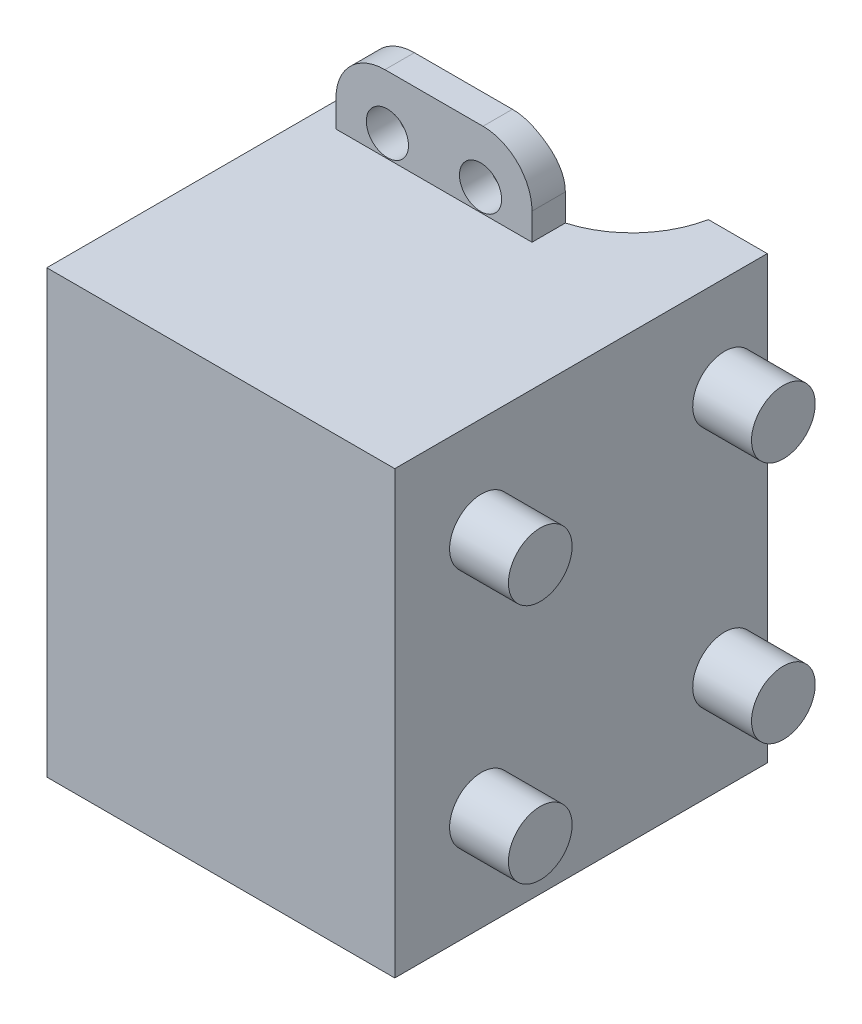
SolidWorks part; units mm, degrees
ref_plane "Front Plane" through (0, 0, 0) normal (0, 0, 1) x (1, 0, 0)
ref_plane "Top Plane" through (0, 0, 0) normal (0, 1, 0) x (1, 0, 0)
ref_plane "Right Plane" through (0, 0, 0) normal (1, 0, 0) x (0, 0, -1)
sketch "Sketch1" plane through (0, 0, 0) normal (0, 0, 1) x (1, 0, 0)
  line L1 (-13.1579, 24.7807) -> (11.8421, 24.7807)
  line L2 (-13.1579, 24.7807) -> (-13.1579, -20.2193)
  line L3 (-13.1579, -20.2193) -> (11.8421, -20.2193)
  line L4 (11.8421, 24.7807) -> (11.8421, -20.2193)
  dimension "D1" = 25
  dimension "D2" = 45
extrude "Boss-Extrude1" add sketch "Sketch1" along normal blind 30
sketch "Sketch2" plane through (0, 0, 0) normal (0, 0, -1) x (-1, 0, 0)
  line L0 (-11.8421, -20.2193) -> (-11.8421, 24.7807) construction
  line L1 (-9.5921, 22.5307) -> (10.9079, 22.5307)
  line L2 (-9.5921, 22.5307) -> (-9.5921, -17.9693)
  line L3 (-9.5921, -17.9693) -> (10.9079, -17.9693)
  line L4 (10.9079, 22.5307) -> (10.9079, -17.9693)
  line L6 (-11.8421, 24.7807) -> (13.1579, 24.7807) construction
  dimension "D1" = 20.5
  dimension "D2" = 40.5
  dimension "D3" = 2.25
  dimension "D4" = 2.25
extrude "Cut-Extrude1" cut sketch "Sketch2" against normal blind 28
sketch "Sketch3" plane through (0, 0, 0) normal (0, 0, -1) x (-1, 0, 0)
  line L0 (-11.8421, 24.7807) -> (13.1579, 24.7807) construction
  line L1 (-9.3421, 24.7807) -> (10.6579, 24.7807)
  line L2 (-9.3421, 24.7807) -> (-9.3421, 32.5307)
  line L3 (-9.3421, 32.5307) -> (10.6579, 32.5307)
  line L4 (10.6579, 24.7807) -> (10.6579, 32.5307)
  line L5 (13.1579, 24.7807) -> (13.1579, -20.2193) construction
  line L7 (-11.8421, 2.2807) -> (13.1579, 2.2807) construction
  line L8 (-11.8421, -20.2193) -> (-11.8421, 24.7807) construction
  line L9 (-9.3421, -27.9693) -> (10.6579, -27.9693)
  line L10 (10.6579, -20.2193) -> (10.6579, -27.9693)
  line L11 (-9.3421, -20.2193) -> (10.6579, -20.2193)
  line L12 (-9.3421, -20.2193) -> (-9.3421, -27.9693)
  dimension "D1" = 7.75
  dimension "D2" = 20
  dimension "D3" = 2.5
extrude "Boss-Extrude2" add sketch "Sketch3" against normal blind 3
sketch "Sketch5" plane through (0, -17.9693, 0) normal (0, 1, 0) x (1, 0, 0)
  line L0 (9.5921, 0) -> (-10.9079, 0) construction
  line L1 (-4.6579, 0) -> (3.3421, 0)
  line L2 (-4.6579, 0) -> (-4.6579, -28)
  line L3 (-4.6579, -28) -> (3.3421, -28)
  line L4 (3.3421, 0) -> (3.3421, -28)
  line L5 (-10.9079, -28) -> (-10.9079, 0) construction
  dimension "D1" = 8
  dimension "D2" = 6.25
  dimension "D3" = 28
extrude "Cut-Extrude2" cut sketch "Sketch5" against normal blind 2.25
fillet "Fillet1" radius 2 2 edges at (3.3421, -20.2193, 1.5) (-4.6579, -20.2193, 1.5)
sketch "Sketch6" plane through (0, 0, 0) normal (0, 0, -1) x (-1, 0, 0)
  line L0 (-11.8421, 24.7807) -> (-9.3421, 24.7807) construction
  line L1 (10.6579, 24.7807) -> (13.1579, 24.7807) construction
  line L2 (10.6579, 24.7807) -> (10.6579, 32.5307) construction
  line L4 (-11.8421, 2.2807) -> (13.1579, 2.2807) construction
  line L5 (-11.8421, -20.2193) -> (-11.8421, 24.7807) construction
  line L6 (13.1579, 24.7807) -> (13.1579, -20.2193) construction
  circle A0 centre (-4.0921, 27.0307) radius 2.15
  circle A1 centre (5.4079, 27.0307) radius 2.15
  circle A2 centre (5.4079, -22.4693) radius 2.15
  circle A3 centre (-4.0921, -22.4693) radius 2.15
  dimension "D1" = 2.25
  dimension "D2" = 2.25
  dimension "D3" = 9.5
  dimension "D4" = 5.25
extrude "Cut-Extrude3" cut sketch "Sketch6" against normal blind 4
fillet "Fillet2" radius 5 4 edges at (9.3421, -27.9693, 1.5) (-10.6579, -27.9693, 1.5) (-10.6579, 32.5307, 1.5) (9.3421, 32.5307, 1.5)
sketch "Sketch8" plane through (11.8421, 0, 0) normal (1, 0, 0) x (0, 0, -1)
  line L4 (0, -20.2193) -> (0, 24.7807)
  line L5 (0, 24.7807) -> (-30, 24.7807)
  line L6 (-30, 24.7807) -> (-30, -20.2193)
  line L7 (-30, -20.2193) -> (0, -20.2193)
  line L8 (0, -20.2193) -> (0, 24.7807)
  line L9 (0, 24.7807) -> (-30, 24.7807)
  line L10 (-30, 24.7807) -> (-30, -20.2193)
  line L11 (-30, -20.2193) -> (0, -20.2193)
  dimension "D1" = 0
extrude "Boss-Extrude3" add sketch "Sketch8" along normal blind 10.5
sketch "Sketch13" plane through (0, 0, 0) normal (0, 0, -1) x (-1, 0, 0)
  line L0 (-9.3421, -20.2193) -> (-22.3421, -20.2193) construction
  line L1 (-22.3421, 24.7807) -> (-16.3421, 24.7807)
  line L2 (-22.3421, 24.7807) -> (-22.3421, -20.2193)
  line L3 (-22.3421, -20.2193) -> (-16.3421, -20.2193)
  line L4 (-16.3421, 24.7807) -> (-16.3421, -20.2193)
  dimension "D1" = 6
extrude "Boss-Extrude6" add sketch "Sketch13" along normal blind 8
fillet "Fillet4" radius 10 1 edges at (16.3421, 2.2807, 0)
sketch "Sketch14" plane through (22.3421, 0, 0) normal (1, 0, 0) x (0, 0, -1)
  line L0 (-21.1561, 22.4356) -> (-21.1561, -16.7441) construction
  line L1 (3.6439, 22.4356) -> (3.6439, -16.7441) construction
  line L2 (-28.514, 14.8737) -> (10.9168, 14.8737) construction
  line L3 (-28.514, -9.7262) -> (10.9168, -9.7262) construction
  circle A0 centre (-21.1561, 14.8737) radius 3.25
  circle A1 centre (3.6439, 15.0738) radius 3.25
  circle A2 centre (3.6439, -9.7262) radius 3.25
  circle A3 centre (-21.1561, -9.7262) radius 3.25
extrude "Boss-Extrude7" add sketch "Sketch14" along normal blind 6
